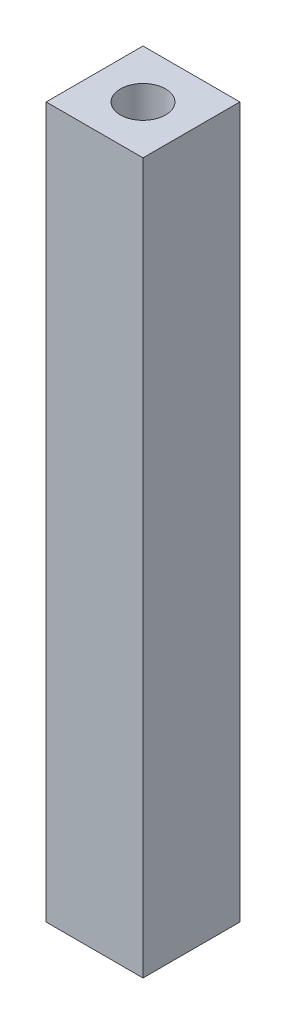
SolidWorks part; units mm, degrees
other "标注1"
sketch "草图3" plane through (-22.25, 4, -10) normal (-0.231, 0.6469, -0.7268) x (-0.9696, -0.2151, 0.1167)
ref_plane "前视基准面" through (0, 0, 0) normal (0, 0, 1) x (1, 0, 0)
ref_plane "上视基准面" through (0, 0, 0) normal (0, 1, 0) x (1, 0, 0)
ref_plane "右视基准面" through (0, 0, 0) normal (1, 0, 0) x (0, 0, -1)
other "Configuration Table"
sketch "草图4" plane through (0, 0, 0) normal (0, 1, 0) x (1, 0, 0)
  line L5 (-1.5, -1.5) -> (1.5, -1.5)
  line L6 (-1.5, -1.5) -> (-1.5, 1.5)
  line L7 (-1.5, 1.5) -> (1.5, 1.5)
  line L8 (1.5, -1.5) -> (1.5, 1.5)
  line L9 (-1.5, -1.5) -> (1.5, 1.5) construction
  line L10 (-1.5, 1.5) -> (1.5, -1.5) construction
  circle A7 centre (0, 0) radius 0.7
  point P7 (20.5009, 1.0656)
  dimension "D1" = 3
  dimension "D2" = 1.4
extrude "凸台-拉伸1" add sketch "草图4" along normal blind 22 contours L5 L8 L7 L6
extrude "切除-拉伸1" cut sketch "草图4<5>" along normal blind 3 contours A7
sketch "草图4<5>" plane through (0, 0, 0) normal (0, 1, 0) x (1, 0, 0) same geometry as "草图4"
extrude "切除-拉伸2" cut sketch "草图4<6>" against normal blind 3 from surface contours A7 starting at face at (0, 22, 0)
sketch "草图4<6>" plane through (0, 0, 0) normal (0, 1, 0) x (1, 0, 0) same geometry as "草图4"
